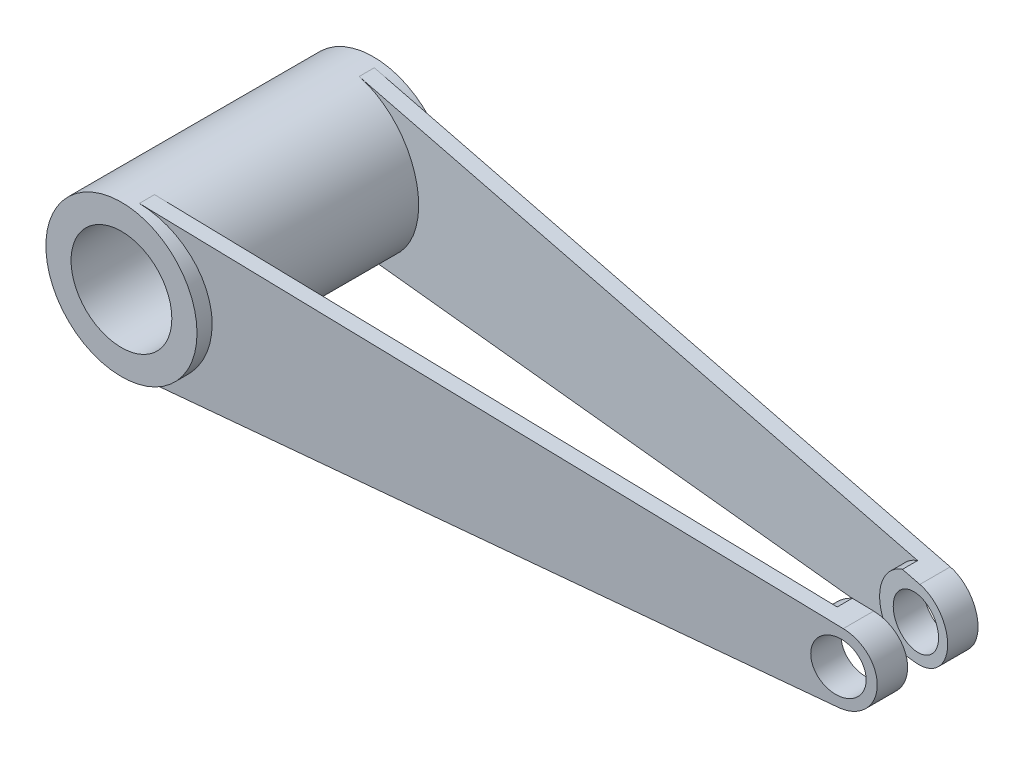
SolidWorks part; units mm, degrees
ref_plane "前基準面" through (0, 0, 0) normal (0, 0, 1) x (1, 0, 0)
ref_plane "上基準面" through (0, 0, 0) normal (0, 1, 0) x (1, 0, 0)
ref_plane "右基準面" through (0, 0, 0) normal (1, 0, 0) x (0, 0, -1)
sketch "草圖1" plane through (0, 0, 0) normal (0, 1, 0) x (1, 0, 0)
  line L0 (0, -25) -> (150, -10)
  line L1 (150, -10) -> (150, 10)
  line L2 (150, 10) -> (0, 25)
  line L3 (0, 25) -> (0, -25)
  point P3 (0, 0)
  dimension "D1" = 20
  dimension "D2" = 50
  dimension "D3" = 150
extrude "填料-伸長1" add sketch "草圖1" along normal blind 60
sketch "草圖2" plane through (0, 0, 0) normal (0, 0, 1) x (1, 0, 0)
  line L0 (0, 0) -> (0, 60)
  line L1 (0, 60) -> (150, 60)
  line L2 (150, 60) -> (150, 0)
  line L3 (0, 0) -> (150, 0) construction
  line L4 (150, 0) -> (143, 0)
  line L5 (0, 0) -> (15, 0)
  line L6 (16.8677, 29.8833) -> (143.8716, 13.9455)
  arc A2 (15, 0) -> (16.8677, 29.8833) centre (15, 15) cw
  arc A3 (143, 0) -> (143.8716, 13.9455) centre (143, 7) ccw
  circle A4 centre (15, 15) radius 10
  circle A5 centre (143, 7) radius 5
  dimension "D1" = 15
  dimension "D2" = 7
  dimension "D3" = 20
  dimension "D4" = 10
extrude "除料-伸長2" cut sketch "草圖2" against normal mid plane 50 contours A4 | L5 A2 L0 | A3 L2 L1 L0 A2 L6 | A5 | A3 L4 L2 region at (148.4364, 1.5636, 0) region at (80.5065, 40.71, 0) region at (3.3505, 3.3505, 0) region at (15, 15, 0) region at (143, 7, 0)
shell "薄殼1" thickness 3 removed face at (80.3696, 21.9144, 0) removed face at (79, 0, 0) removed face at (146.7111, 6.7681, 0) removed face at (7.9815, 15.4387, 0)
sketch "草圖5" plane through (0, 0, 0) normal (0, 0, 1) x (1, 0, 0)
  circle A0 centre (15, 15) radius 10
  circle A1 centre (15, 15) radius 15
  dimension "D1" = 20
  dimension "D2" = 30
extrude "填料-伸長3" add sketch "草圖5" along normal mid plane 50
sketch "草圖6" plane through (0, 0, 0) normal (0, 0, 1) x (1, 0, 0)
  circle A0 centre (143, 7) radius 5
  circle A1 centre (143, 7) radius 7
  dimension "D1" = 10
  dimension "D2" = 14
extrude "填料-伸長4" add sketch "草圖6" along normal mid plane 20
sketch "草圖3" plane through (0, 0, 0) normal (0, 1, 0) x (1, 0, 0)
  line L3 (154.7007, 3.5) -> (154.7007, -3.5)
  line L4 (154.7007, -3.5) -> (135, -5.4701)
  line L5 (140.0288, -7.9822) -> (16.8677, -20.2983) construction
  line L6 (135, -5.4701) -> (135, 5.4701)
  line L10 (154.7007, 3.5) -> (135, 5.4701)
  line L12 (135, 8.485) -> (135, -8.485) construction
  line L13 (16.8677, 20.2983) -> (140.0288, 7.9822) construction
  point P2 (135, 6.985)
  point P4 (149.9059, 5.4299)
  point P10 (135.1153, 8.4735)
  point P11 (135, 8.485)
  dimension "D1" = 3
  dimension "D2" = 3
  dimension "D3" = 7
extrude "除料-伸長4" cut sketch "草圖3" along normal blind 20
